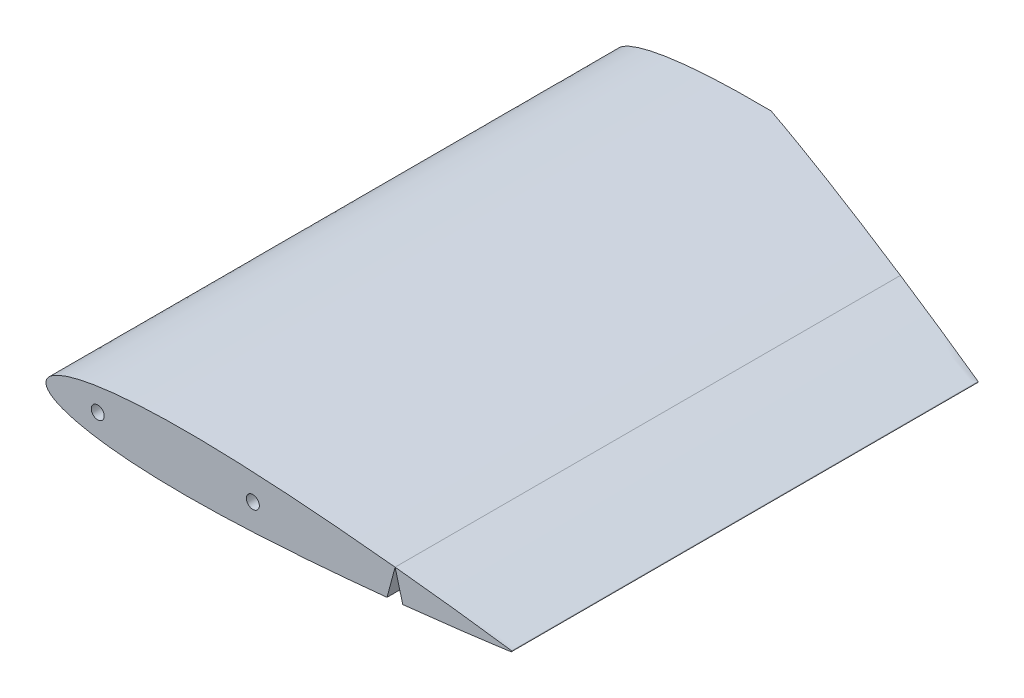
SolidWorks part; units mm, degrees
material "Thornel Mat VMA Foam Core"
ref_plane "Front Plane" through (0, 0, 0) normal (0, 0, 1) x (1, 0, 0)
ref_plane "Top Plane" through (0, 0, 0) normal (0, 1, 0) x (1, 0, 0)
ref_plane "Right Plane" through (0, 0, 0) normal (1, 0, 0) x (0, 0, -1)
curve "Curve1"
  spline degree 3 poles (0.0004, -0.0044, 0) (-0.0002, 0, 0) (0.0004, 0.0044, 0) (0.0023, 0.0087, 0) (0.0053, 0.0128, 0) (0.0094, 0.0167, 0) (0.0147, 0.0206, 0) (0.0211, 0.0243, 0) (0.0286, 0.0279, 0) (0.0372, 0.0313, 0) (0.0468, 0.0347, 0) (0.0576, 0.0378, 0) (0.0693, 0.0408, 0) (0.0821, 0.0436, 0) (0.0958, 0.0462, 0) (0.1104, 0.0486, 0) (0.126, 0.0507, 0) (0.1425, 0.0527, 0) (0.1597, 0.0544, 0) (0.1778, 0.056, 0) (0.1966, 0.0572, 0) (0.2162, 0.0583, 0) (0.2364, 0.0591, 0) (0.2572, 0.0596, 0) (0.2786, 0.06, 0) (0.3005, 0.0601, 0) (0.3228, 0.0599, 0) (0.3456, 0.0596, 0) (0.3688, 0.0591, 0) (0.3922, 0.0583, 0) (0.4159, 0.0574, 0) (0.4398, 0.0563, 0) (0.4638, 0.0551, 0) (0.4879, 0.0537, 0) (0.5121, 0.0522, 0) (0.5362, 0.0505, 0) (0.5602, 0.0488, 0) (0.5841, 0.0469, 0) (0.6078, 0.045, 0) (0.6313, 0.043, 0) (0.6544, 0.0409, 0) (0.6772, 0.0388, 0) (0.6995, 0.0367, 0) (0.7214, 0.0345, 0) (0.7428, 0.0324, 0) (0.7636, 0.0302, 0) (0.7838, 0.028, 0) (0.8033, 0.0259, 0) (0.8222, 0.0238, 0) (0.8402, 0.0217, 0) (0.8575, 0.0196, 0) (0.874, 0.0177, 0) (0.8895, 0.0158, 0) (0.9042, 0.014, 0) (0.9179, 0.0122, 0) (0.9307, 0.0106, 0) (0.9424, 0.0091, 0) (0.9531, 0.0077, 0) (0.9627, 0.0064, 0) (0.9713, 0.0052, 0) (0.9788, 0.0042, 0) (0.9851, 0.0033, 0) (0.9903, 0.0026, 0) (0.9944, 0.002, 0) (0.9973, 0.0017, 0) (0.999, 0.0013, 0) (1.0007, 0.0014, 0) (1.0007, -0.0014, 0) (0.999, -0.0013, 0) (0.9973, -0.0017, 0) (0.9944, -0.002, 0) (0.9903, -0.0026, 0) (0.9851, -0.0033, 0) (0.9788, -0.0042, 0) (0.9713, -0.0052, 0) (0.9627, -0.0064, 0) (0.9531, -0.0077, 0) (0.9424, -0.0091, 0) (0.9307, -0.0106, 0) (0.9179, -0.0122, 0) (0.9042, -0.014, 0) (0.8895, -0.0158, 0) (0.874, -0.0177, 0) (0.8575, -0.0196, 0) (0.8402, -0.0217, 0) (0.8222, -0.0238, 0) (0.8033, -0.0259, 0) (0.7838, -0.028, 0) (0.7636, -0.0302, 0) (0.7428, -0.0324, 0) (0.7214, -0.0345, 0) (0.6995, -0.0367, 0) (0.6772, -0.0388, 0) (0.6544, -0.0409, 0) (0.6313, -0.043, 0) (0.6078, -0.045, 0) (0.5841, -0.0469, 0) (0.5602, -0.0488, 0) (0.5362, -0.0505, 0) (0.5121, -0.0522, 0) (0.4879, -0.0537, 0) (0.4638, -0.0551, 0) (0.4398, -0.0563, 0) (0.4159, -0.0574, 0) (0.3922, -0.0583, 0) (0.3688, -0.0591, 0) (0.3456, -0.0596, 0) (0.3228, -0.0599, 0) (0.3005, -0.0601, 0) (0.2786, -0.06, 0) (0.2572, -0.0596, 0) (0.2364, -0.0591, 0) (0.2162, -0.0583, 0) (0.1966, -0.0572, 0) (0.1778, -0.056, 0) (0.1597, -0.0544, 0) (0.1425, -0.0527, 0) (0.126, -0.0507, 0) (0.1104, -0.0486, 0) (0.0958, -0.0462, 0) (0.0821, -0.0436, 0) (0.0693, -0.0408, 0) (0.0576, -0.0378, 0) (0.0468, -0.0347, 0) (0.0372, -0.0313, 0) (0.0286, -0.0279, 0) (0.0211, -0.0243, 0) (0.0147, -0.0206, 0) (0.0094, -0.0167, 0) (0.0053, -0.0128, 0) (0.0023, -0.0087, 0) (0.0004, -0.0044, 0) (-0.0002, 0, 0) (0.0004, 0.0044, 0) knots -0.006773 -0.004321 -0.002106 0 0.002106 0.004321 0.006773 0.009557 0.012734 0.016343 0.020406 0.024934 0.029933 0.035402 0.041337 0.047732 0.054575 0.061857 0.069565 0.077682 0.086195 0.095084 0.104333 0.113922 0.123829 0.134035 0.144516 0.155249 0.16621 0.177376 0.18872 0.200217 0.21184 0.223563 0.235359 0.2472 0.259058 0.270907 0.282718 0.294465 0.306118 0.317651 0.329037 0.340249 0.35126 0.362045 0.372579 0.382836 0.392793 0.402425 0.411711 0.420628 0.429156 0.437273 0.444962 0.452203 0.458979 0.465275 0.471075 0.476366 0.481134 0.485369 0.48906 0.492198 0.494776 0.496788 0.498228 0.499094 0.499383 0.500617 0.500906 0.501772 0.503212 0.505224 0.507802 0.51094 0.514631 0.518866 0.523634 0.528925 0.534725 0.541021 0.547797 0.555038 0.562727 0.570844 0.579372 0.588289 0.597575 0.607207 0.617164 0.627421 0.637955 0.64874 0.659751 0.670963 0.682349 0.693882 0.705535 0.717282 0.729093 0.740942 0.7528 0.764641 0.776437 0.78816 0.799783 0.81128 0.822624 0.83379 0.844751 0.855484 0.865965 0.876171 0.886078 0.895667 0.904916 0.913805 0.922318 0.930435 0.938143 0.945425 0.952268 0.958663 0.964598 0.970067 0.975066 0.979594 0.983657 0.987266 0.990443 0.993227 0.995679 0.997894 1 1.002106 1.004321 1.006773 periodic
sketch "Sketch1" plane through (0, 0, 0) normal (0, 0, 1) x (1, 0, 0)
  line L0 (228.6, 0) -> (0, 0) construction
  line L1 (0.5505, 0) -> (-0.5505, 0) construction
  line L2 (0, 0) -> (0, 0.0037) construction
  line L3 (0, -0.0661) -> (0, 0.0661) construction
  spline S1 degree 3 poles (0.0941, 1.0023) (-0.0459, 0) (0.0941, -1.0023) (0.5163, -1.979) (1.2063, -2.9191) (2.1555, -3.8265) (3.3611, -4.7045) (4.8212, -5.5539) (6.5336, -6.3738) (8.4955, -7.1622) (10.7028, -7.9169) (13.1508, -8.6353) (15.8342, -9.3147) (18.7469, -9.9527) (21.8822, -10.5465) (25.2329, -11.0942) (28.7913, -11.5933) (32.549, -12.0423) (36.4974, -12.4394) (40.6273, -12.7838) (44.929, -13.0744) (49.3924, -13.3108) (54.0073, -13.4932) (58.7627, -13.6218) (63.6477, -13.6973) (68.6508, -13.7209) (73.7603, -13.694) (78.9643, -13.6184) (84.2506, -13.4961) (89.607, -13.3294) (95.0208, -13.1208) (100.4795, -12.873) (105.9703, -12.5887) (111.4804, -12.2709) (116.997, -11.9225) (122.507, -11.5464) (127.9978, -11.1457) (133.4564, -10.7232) (138.8702, -10.2819) (144.2264, -9.8246) (149.5125, -9.354) (154.7163, -8.873) (159.8255, -8.3842) (164.8283, -7.89) (169.7129, -7.3931) (174.468, -6.8959) (179.0824, -6.4008) (183.5453, -5.9102) (187.8464, -5.4263) (191.9755, -4.9516) (195.9231, -4.4883) (199.6799, -4.0386) (203.2372, -3.6048) (206.5865, -3.1892) (209.7203, -2.7938) (212.631, -2.4208) (215.3118, -2.0722) (217.7567, -1.7502) (219.9598, -1.4564) (221.9158, -1.1925) (223.6207, -0.9608) (225.0694, -0.7609) (226.261, -0.599) (227.1864, -0.4629) (227.8589, -0.3857) (228.2452, -0.3022) (228.6415, -0.3098) (228.6415, 0.3098) (228.2452, 0.3022) (227.8589, 0.3857) (227.1864, 0.4629) (226.261, 0.599) (225.0694, 0.7609) (223.6207, 0.9608) (221.9158, 1.1925) (219.9598, 1.4564) (217.7567, 1.7502) (215.3118, 2.0722) (212.631, 2.4208) (209.7203, 2.7938) (206.5865, 3.1892) (203.2372, 3.6048) (199.6799, 4.0386) (195.9231, 4.4883) (191.9755, 4.9516) (187.8464, 5.4263) (183.5453, 5.9102) (179.0824, 6.4008) (174.468, 6.8959) (169.7129, 7.3931) (164.8283, 7.89) (159.8255, 8.3842) (154.7163, 8.873) (149.5125, 9.354) (144.2264, 9.8246) (138.8702, 10.2819) (133.4564, 10.7232) (127.9978, 11.1457) (122.507, 11.5464) (116.997, 11.9225) (111.4804, 12.2709) (105.9703, 12.5887) (100.4795, 12.873) (95.0208, 13.1208) (89.607, 13.3294) (84.2506, 13.4961) (78.9643, 13.6184) (73.7603, 13.694) (68.6508, 13.7209) (63.6477, 13.6973) (58.7627, 13.6218) (54.0073, 13.4932) (49.3924, 13.3108) (44.929, 13.0744) (40.6273, 12.7838) (36.4974, 12.4394) (32.549, 12.0423) (28.7913, 11.5933) (25.2329, 11.0942) (21.8822, 10.5465) (18.7469, 9.9527) (15.8342, 9.3147) (13.1508, 8.6353) (10.7028, 7.9169) (8.4955, 7.1622) (6.5336, 6.3738) (4.8212, 5.5539) (3.3611, 4.7045) (2.1555, 3.8265) (1.2063, 2.9191) (0.5163, 1.979) (0.0941, 1.0023) (-0.0459, 0) (0.0941, -1.0023) knots -0.006773 -0.004321 -0.002106 0 0.002106 0.004321 0.006773 0.009557 0.012734 0.016343 0.020406 0.024934 0.029933 0.035402 0.041337 0.047732 0.054575 0.061857 0.069565 0.077682 0.086195 0.095084 0.104333 0.113922 0.123829 0.134035 0.144516 0.155249 0.16621 0.177376 0.18872 0.200217 0.21184 0.223563 0.235359 0.2472 0.259058 0.270907 0.282718 0.294465 0.306118 0.317651 0.329037 0.340249 0.35126 0.362045 0.372579 0.382836 0.392793 0.402425 0.411711 0.420628 0.429156 0.437273 0.444962 0.452203 0.458979 0.465275 0.471075 0.476366 0.481134 0.485369 0.48906 0.492198 0.494776 0.496788 0.498228 0.499094 0.499383 0.500617 0.500906 0.501772 0.503212 0.505224 0.507802 0.51094 0.514631 0.518866 0.523634 0.528925 0.534725 0.541021 0.547797 0.555038 0.562727 0.570844 0.579372 0.588289 0.597575 0.607207 0.617164 0.627421 0.637955 0.64874 0.659751 0.670963 0.682349 0.693882 0.705535 0.717282 0.729093 0.740942 0.7528 0.764641 0.776437 0.78816 0.799783 0.81128 0.822624 0.83379 0.844751 0.855484 0.865965 0.876171 0.886078 0.895667 0.904916 0.913805 0.922318 0.930435 0.938143 0.945425 0.952268 0.958663 0.964598 0.970067 0.975066 0.979594 0.983657 0.987266 0.990443 0.993227 0.995679 0.997894 1 1.002106 1.004321 1.006773 only from (0, 0) to (0, 0)
  dimension "D1" = 228.6
extrude "Boss-Extrude1" add sketch "Sketch1" along normal blind 279.908
sketch "Sketch2" plane through (0, 0, 0) normal (0, 0, -1) x (-1, 0, 0)
  line L0 (125.7781, 0) -> (-125.7781, 0) construction
  circle A0 centre (-25.4, 0) radius 3.175
  dimension "D1" = 6.35
  dimension "D2" = 25.4
extrude "Cut-Extrude1" cut sketch "Sketch2" against normal through all
sketch "Sketch3" plane through (0, 0, 0) normal (0, 1, 0) x (1, 0, 0)
  line L0 (228.655, 0) -> (228.6, -50.8)
  line L1 (-15.093, 0) -> (15.093, 0) construction
  line L2 (228.6, -279.908) -> (228.6, 0) construction
  line L3 (228.6, -50.8) -> (76.2, 0)
  line L4 (76.2, 0) -> (228.655, 0)
  dimension "D1" = 152.4
  dimension "D2" = 50.8
extrude "Cut-Extrude2" cut sketch "Sketch3" against normal up to next and the other way up to next
sketch "Sketch4" plane through (0, 0, 279.908) normal (0, 0, 1) x (1, 0, 0)
  line L0 (171.45, 0) -> (171.45, 54.9085) construction
  line L1 (125.7781, 0) -> (-125.7781, 0) construction
  line L2 (0, -15.093) -> (0, 15.093) construction
  line L3 (171.45, 7.2108) -> (167.4761, -7.6201)
  line L5 (175.2083, -6.8152) -> (171.45, 7.2108)
  arc A0 (175.2083, -6.8152) -> (167.4761, -7.6201) centre (170.3228, 2.5746) cw
  spline S1 degree 3 poles (0.0941, 1.0023) (-0.0459, 0) (0.0941, -1.0023) (0.5163, -1.979) (1.2063, -2.9191) (2.1555, -3.8265) (3.3611, -4.7045) (4.8212, -5.5539) (6.5336, -6.3738) (8.4955, -7.1622) (10.7028, -7.9169) (13.1508, -8.6353) (15.8342, -9.3147) (18.7469, -9.9527) (21.8822, -10.5465) (25.2329, -11.0942) (28.7913, -11.5933) (32.549, -12.0423) (36.4974, -12.4394) (40.6273, -12.7838) (44.929, -13.0744) (49.3924, -13.3108) (54.0073, -13.4932) (58.7627, -13.6218) (63.6477, -13.6973) (68.6508, -13.7209) (73.7603, -13.694) (78.9643, -13.6184) (84.2506, -13.4961) (89.607, -13.3294) (95.0208, -13.1208) (100.4795, -12.873) (105.9703, -12.5887) (111.4804, -12.2709) (116.997, -11.9225) (122.507, -11.5464) (127.9978, -11.1457) (133.4564, -10.7232) (138.8702, -10.2819) (144.2264, -9.8246) (149.5125, -9.354) (154.7163, -8.873) (159.8255, -8.3842) (164.8283, -7.89) (169.7129, -7.3931) (174.468, -6.8959) (179.0824, -6.4008) (183.5453, -5.9102) (187.8464, -5.4263) (191.9755, -4.9516) (195.9231, -4.4883) (199.6799, -4.0386) (203.2372, -3.6048) (206.5865, -3.1892) (209.7203, -2.7938) (212.631, -2.4208) (215.3118, -2.0722) (217.7567, -1.7502) (219.9598, -1.4564) (221.9158, -1.1925) (223.6207, -0.9608) (225.0694, -0.7609) (226.261, -0.599) (227.1864, -0.4629) (227.8589, -0.3857) (228.2452, -0.3022) (228.6415, -0.3098) (228.6415, 0.3098) (228.2452, 0.3022) (227.8589, 0.3857) (227.1864, 0.4629) (226.261, 0.599) (225.0694, 0.7609) (223.6207, 0.9608) (221.9158, 1.1925) (219.9598, 1.4564) (217.7567, 1.7502) (215.3118, 2.0722) (212.631, 2.4208) (209.7203, 2.7938) (206.5865, 3.1892) (203.2372, 3.6048) (199.6799, 4.0386) (195.9231, 4.4883) (191.9755, 4.9516) (187.8464, 5.4263) (183.5453, 5.9102) (179.0824, 6.4008) (174.468, 6.8959) (169.7129, 7.3931) (164.8283, 7.89) (159.8255, 8.3842) (154.7163, 8.873) (149.5125, 9.354) (144.2264, 9.8246) (138.8702, 10.2819) (133.4564, 10.7232) (127.9978, 11.1457) (122.507, 11.5464) (116.997, 11.9225) (111.4804, 12.2709) (105.9703, 12.5887) (100.4795, 12.873) (95.0208, 13.1208) (89.607, 13.3294) (84.2506, 13.4961) (78.9643, 13.6184) (73.7603, 13.694) (68.6508, 13.7209) (63.6477, 13.6973) (58.7627, 13.6218) (54.0073, 13.4932) (49.3924, 13.3108) (44.929, 13.0744) (40.6273, 12.7838) (36.4974, 12.4394) (32.549, 12.0423) (28.7913, 11.5933) (25.2329, 11.0942) (21.8822, 10.5465) (18.7469, 9.9527) (15.8342, 9.3147) (13.1508, 8.6353) (10.7028, 7.9169) (8.4955, 7.1622) (6.5336, 6.3738) (4.8212, 5.5539) (3.3611, 4.7045) (2.1555, 3.8265) (1.2063, 2.9191) (0.5163, 1.979) (0.0941, 1.0023) (-0.0459, 0) (0.0941, -1.0023) knots -0.006773 -0.004321 -0.002106 0 0.002106 0.004321 0.006773 0.009557 0.012734 0.016343 0.020406 0.024934 0.029933 0.035402 0.041337 0.047732 0.054575 0.061857 0.069565 0.077682 0.086195 0.095084 0.104333 0.113922 0.123829 0.134035 0.144516 0.155249 0.16621 0.177376 0.18872 0.200217 0.21184 0.223563 0.235359 0.2472 0.259058 0.270907 0.282718 0.294465 0.306118 0.317651 0.329037 0.340249 0.35126 0.362045 0.372579 0.382836 0.392793 0.402425 0.411711 0.420628 0.429156 0.437273 0.444962 0.452203 0.458979 0.465275 0.471075 0.476366 0.481134 0.485369 0.48906 0.492198 0.494776 0.496788 0.498228 0.499094 0.499383 0.500617 0.500906 0.501772 0.503212 0.505224 0.507802 0.51094 0.514631 0.518866 0.523634 0.528925 0.534725 0.541021 0.547797 0.555038 0.562727 0.570844 0.579372 0.588289 0.597575 0.607207 0.617164 0.627421 0.637955 0.64874 0.659751 0.670963 0.682349 0.693882 0.705535 0.717282 0.729093 0.740942 0.7528 0.764641 0.776437 0.78816 0.799783 0.81128 0.822624 0.83379 0.844751 0.855484 0.865965 0.876171 0.886078 0.895667 0.904916 0.913805 0.922318 0.930435 0.938143 0.945425 0.952268 0.958663 0.964598 0.970067 0.975066 0.979594 0.983657 0.987266 0.990443 0.993227 0.995679 0.997894 1 1.002106 1.004321 1.006773 only from (0, 0) to (0, 0) construction
  dimension "D1" = 171.45
  dimension "D3" = 15
  dimension "D4" = 15
extrude "Cut-Extrude4" cut sketch "Sketch4" against normal up to next
sketch "Sketch5" plane through (0, 0, 0) normal (0, 0, -1) x (-1, 0, 0)
  line L0 (125.7781, 0) -> (-125.7781, 0) construction
  line L1 (0, 15.093) -> (0, -15.093) construction
  circle A0 centre (-101.6, 0) radius 3.175
  dimension "D1" = 6.35
  dimension "D2" = 101.6
extrude "Cut-Extrude5" cut sketch "Sketch5" against normal through all
